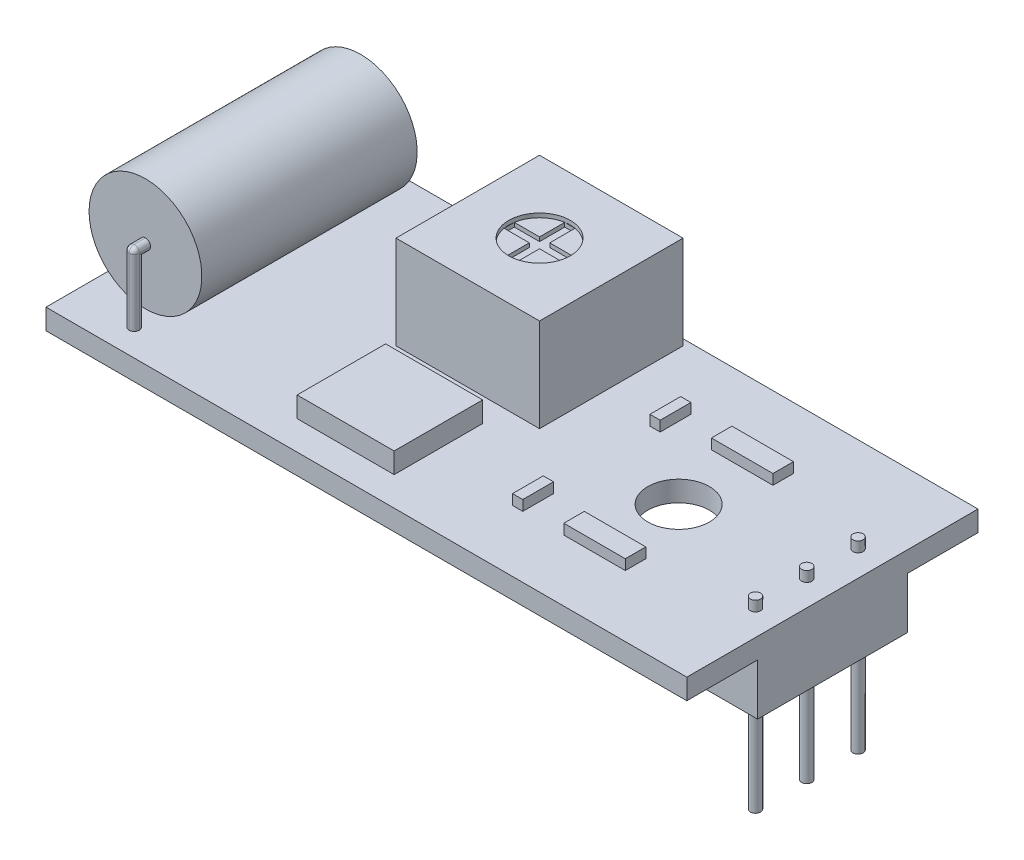
SolidWorks part; units mm, degrees
ref_plane "Plan de face" through (0, 0, 0) normal (0, 0, 1) x (1, 0, 0)
ref_plane "Plan de dessus" through (0, 0, 0) normal (0, 1, 0) x (1, 0, 0)
ref_plane "Plan de droite" through (0, 0, 0) normal (1, 0, 0) x (0, 0, -1)
sketch "Esquisse1" plane through (0, 0, 0) normal (0, 1, 0) x (1, 0, 0)
  line L1 (0, 0) -> (-31.25, 0)
  line L2 (0, 0) -> (0, 14.2)
  line L3 (0, 14.2) -> (-31.25, 14.2)
  line L4 (-31.25, 0) -> (-31.25, 14.2)
  dimension "D1" = 31.25
  dimension "D2" = 14.2
extrude "Boss.-Extru.1" add sketch "Esquisse1" along normal blind 1
sketch "Esquisse2" plane through (0, 1, 0) normal (0, 1, 0) x (1, 0, 0)
  line L0 (-31.25, 14.2) -> (-28.25, 14.2) construction
  line L1 (0, 14.2) -> (-31.25, 14.2) construction
  line L2 (-28.25, 14.2) -> (-28.25, 0) construction
  line L3 (-31.25, 0) -> (0, 0) construction
  line L4 (-28.25, 0) -> (-31.25, 0) construction
  line L5 (-28.25, 14.2) -> (-28.25, 12.9) construction
  line L6 (-28.25, 0) -> (-28.25, 1.3) construction
  line L8 (-28, 12.65) -> (-28.5, 12.65)
  line L9 (-28, 12.65) -> (-28, 13.15)
  line L10 (-28, 13.15) -> (-28.5, 13.15)
  line L11 (-28.5, 12.65) -> (-28.5, 13.15)
  line L12 (-28, 12.65) -> (-28.5, 13.15) construction
  line L13 (-28, 13.15) -> (-28.5, 12.65) construction
  line L14 (-28, 1.05) -> (-28.5, 1.05)
  line L15 (-28, 1.05) -> (-28, 1.55)
  line L16 (-28, 1.55) -> (-28.5, 1.55)
  line L17 (-28.5, 1.05) -> (-28.5, 1.55)
  line L18 (-28, 1.05) -> (-28.5, 1.55) construction
  line L19 (-28, 1.55) -> (-28.5, 1.05) construction
  dimension "D1" = 3
  dimension "D2" = 1.3
  dimension "D3" = 1.3
  dimension "D4" = 0.5
  dimension "D5" = 0.5
  dimension "D6" = 0.5
  dimension "D7" = 0.5
extrude "Boss.-Extru.2" add sketch "Esquisse2" along normal blind 3.5
sketch "Esquisse3" plane through (0, 0, -12.65) normal (0, 0, 1) x (1, 0, 0)
  line L0 (-28.5, 4.5) -> (-28.5, 1) construction
  line L1 (-28, 4.5) -> (-28.5, 4.5)
  line L2 (-28, 4.5) -> (-28, 4)
  line L3 (-28, 4) -> (-28.5, 4)
  line L4 (-28.5, 4.5) -> (-28.5, 4)
  dimension "D1" = 0.5
extrude "Boss.-Extru.3" add sketch "Esquisse3" along normal blind 0.3
sketch "Esquisse4" plane through (0, 0, -1.55) normal (0, 0, -1) x (-1, 0, 0)
  line L0 (28, 4.5) -> (28, 1) construction
  line L1 (28.5, 4.5) -> (28, 4.5)
  line L2 (28.5, 4.5) -> (28.5, 4)
  line L3 (28.5, 4) -> (28, 4)
  line L4 (28, 4.5) -> (28, 4)
  dimension "D1" = 0.5
extrude "Boss.-Extru.4" add sketch "Esquisse4" along normal blind 0.3
sketch "Esquisse5" plane through (0, 0, -12.35) normal (0, 0, 1) x (1, 0, 0)
  line L0 (-28.5, 4.5) -> (-28, 4) construction
  circle A0 centre (-28.25, 4.25) radius 2.75
  dimension "D1" = 5.5
extrude "Boss.-Extru.5" add sketch "Esquisse5" along normal blind 10.5
sketch "Esquisse6" plane through (0, 1, 0) normal (0, 1, 0) x (1, 0, 0)
  line L0 (0, 14.2) -> (-31.25, 14.2) construction
  line L1 (-21.0823, 6.9) -> (-14.0823, 6.9)
  line L2 (-21.0823, 6.9) -> (-21.0823, 13.9)
  line L3 (-21.0823, 13.9) -> (-14.0823, 13.9)
  line L4 (-14.0823, 6.9) -> (-14.0823, 13.9)
  dimension "D1" = 7
  dimension "D2" = 7
  dimension "D3" = 0.3
extrude "Boss.-Extru.6" add sketch "Esquisse6" along normal blind 4.55
sketch "Esquisse7" plane through (0, 5.55, 0) normal (0, 1, 0) x (1, 0, 0)
  line L0 (-21.0823, 6.9) -> (-14.0823, 13.9) construction
  line L1 (-14.0823, 13.9) -> (-21.0823, 13.9) construction
  line L2 (-14.0823, 13.9) -> (-21.0823, 13.9) construction
  circle A0 centre (-17.5823, 10.4) radius 1.5
  dimension "D1" = 3
extrude "Enlèv. mat.-Extru.1" cut sketch "Esquisse7" against normal blind 0.2
sketch "Esquisse8" plane through (0, 5.35, 0) normal (0, 1, 0) x (1, 0, 0)
  line L0 (-21.0823, 6.9) -> (-14.0823, 13.9) construction
  line L2 (-16.1032, 10.65) -> (-19.0613, 10.65)
  line L3 (-16.1032, 10.65) -> (-16.1032, 10.15)
  line L4 (-16.1032, 10.15) -> (-19.0613, 10.15)
  line L5 (-19.0613, 10.65) -> (-19.0613, 10.15)
  line L6 (-16.1032, 10.65) -> (-19.0613, 10.15) construction
  line L7 (-16.1032, 10.15) -> (-19.0613, 10.65) construction
  line L8 (-17.3323, 11.879) -> (-17.8323, 11.879)
  line L9 (-17.3323, 11.879) -> (-17.3323, 8.921)
  line L10 (-17.3323, 8.921) -> (-17.8323, 8.921)
  line L11 (-17.8323, 11.879) -> (-17.8323, 8.921)
  line L12 (-17.3323, 11.879) -> (-17.8323, 8.921) construction
  line L13 (-17.3323, 8.921) -> (-17.8323, 11.879) construction
  circle A0 centre (-17.5823, 10.4) radius 1.5 construction
  circle A1 centre (-17.5823, 10.4) radius 1.5 construction
  point P4 (-17.5823, 10.4)
  point P11 (-17.5823, 10.4)
  dimension "D1" = 0.5
  dimension "D2" = 0.5
extrude "Enlèv. mat.-Extru.2" cut sketch "Esquisse8" against normal blind 0.2 contours L11 L2 L5 L4 | L4 L11 L10 L9 | L2 L9 L4 L3 | L8 L11 L2 L9 | L2 L11 L4 L9 region at (-16.7177, 5.35, -10.4) region at (-17.5823, 5.35, -10.4) region at (-17.5823, 5.35, -11.2645) region at (-18.4468, 5.35, -10.4) region at (-17.5823, 5.35, -9.5355)
sketch "Esquisse9" plane through (0, 1, 0) normal (0, 1, 0) x (1, 0, 0)
  line L0 (-31.25, 0) -> (0, 0) construction
  line L1 (-20.4183, 1.4145) -> (-15.6873, 1.4145)
  line L2 (-20.4183, 1.4145) -> (-20.4183, 5.7305)
  line L3 (-20.4183, 5.7305) -> (-15.6873, 5.7305)
  line L4 (-15.6873, 1.4145) -> (-15.6873, 5.7305)
  line L5 (-9, 3) -> (-6, 3)
  line L6 (-9, 3) -> (-9, 4)
  line L7 (-9, 4) -> (-6, 4)
  line L8 (-6, 3) -> (-6, 4)
  line L9 (-9, 10.2) -> (-6, 10.2)
  line L10 (-9, 10.2) -> (-9, 11.2)
  line L11 (-9, 11.2) -> (-6, 11.2)
  line L12 (-6, 10.2) -> (-6, 11.2)
  line L13 (-11.5, 3) -> (-11, 3)
  line L14 (-11.5, 3) -> (-11.5, 4.5)
  line L15 (-11.5, 4.5) -> (-11, 4.5)
  line L16 (-11, 3) -> (-11, 4.5)
  line L17 (-11.5, 9.7) -> (-11, 9.7)
  line L18 (-11.5, 9.7) -> (-11.5, 11.2)
  line L19 (-11.5, 11.2) -> (-11, 11.2)
  line L20 (-11, 9.7) -> (-11, 11.2)
  line L21 (0, 14.2) -> (-31.25, 14.2) construction
  line L22 (0, 0) -> (0, 14.2) construction
  line L23 (-7.5, 4) -> (-7.5, 10.2) construction
  point P26 (-11, 3.75)
  point P27 (-11.25, 11.2)
  dimension "D1" = 1
  dimension "D2" = 1
  dimension "D3" = 3
  dimension "D4" = 3
  dimension "D5" = 1.5
  dimension "D6" = 1.5
  dimension "D7" = 0.5
  dimension "D8" = 0.5
  dimension "D9" = 3
  dimension "D10" = 3
  dimension "D11" = 6
  dimension "D12" = 6
  dimension "D13" = 2
  dimension "D14" = 2
  dimension "D15" = 0
  dimension "D16" = 0
extrude "Boss.-Extru.7" add sketch "Esquisse9" along normal blind 0.5
sketch "Esquisse10" plane through (0, 1.5, 0) normal (0, 1, 0) x (1, 0, 0)
  line L1 (-20.4183, 1.4145) -> (-15.6873, 1.4145)
  line L2 (-20.4183, 1.4145) -> (-20.4183, 5.7305)
  line L3 (-20.4183, 5.7305) -> (-15.6873, 5.7305)
  line L4 (-15.6873, 1.4145) -> (-15.6873, 5.7305)
extrude "Boss.-Extru.8" add sketch "Esquisse10" along normal blind 0.5
sketch "Esquisse11" plane through (0, 1, 0) normal (0, 1, 0) x (1, 0, 0)
  line L0 (-7.5, 4) -> (-7.5, 10.2) construction
  line L1 (-6, 4) -> (-9, 4) construction
  line L2 (-9, 10.2) -> (-6, 10.2) construction
  circle A0 centre (-7.5, 7.1) radius 1.5
  dimension "D1" = 3
extrude "Enlèv. mat.-Extru.3" cut sketch "Esquisse11" against normal blind 22.5
sketch "Esquisse12" plane through (0, 0, 0) normal (0, -1, 0) x (-1, 0, 0)
  line L0 (0, 0) -> (0, 14.2) construction
  line L1 (0, 10.75) -> (2.5, 10.75)
  line L2 (0, 10.75) -> (0, 3.45)
  line L3 (0, 3.45) -> (2.5, 3.45)
  line L4 (2.5, 10.75) -> (2.5, 3.45)
  line L5 (0, 14.2) -> (31.25, 14.2) construction
  dimension "D1" = 7.3
  dimension "D2" = 3.45
  dimension "D3" = 2.5
extrude "Boss.-Extru.9" add sketch "Esquisse12" along normal blind 2.5
sketch "Esquisse13" plane through (0, -2.5, 0) normal (0, -1, 0) x (-1, 0, 0)
  line L0 (1.25, 10.75) -> (1.25, 9.6) construction
  line L1 (2.5, 10.75) -> (0, 10.75) construction
  line L2 (1.25, 9.6) -> (1.25, 4.1615) construction
  line L3 (1.25, 4.1615) -> (1.25, 3.45) construction
  line L4 (0, 3.45) -> (2.5, 3.45) construction
  circle A0 centre (1.25, 9.6) radius 0.25
  circle A1 centre (1.25, 7.1) radius 0.25
  circle A2 centre (1.25, 4.6) radius 0.25
  dimension "D2" = 0.5
  dimension "D1" = 1.15
  dimension "D3" = 3
extrude "Boss.-Extru.10" add sketch "Esquisse13" along normal blind 5 and the other way blind 4
fillet "Congé1" radius 0.25 4 edges at (-28.5, 2.5, -1.55) (-28, 2.75, -1.05) (-28, 2.5, -1.55) (-28.5, 2.75, -1.05)
fillet "Congé2" radius 0.25 6 edges at (-28.5, 4, -1.575) (-28, 4, -1.575) (-28.4268, 4.5, -1.1232) (-28.0732, 4.5, -1.1232) (-28.5, 4.5, -1.575) (-28, 4.5, -1.575)
fillet "Congé3" radius 0.25 8 edges at (-28, 4, -12.5) (-28, 2.5, -12.65) (-28, 2.75, -13.15) (-28, 4.5, -12.75) (-28.5, 2.5, -12.65) (-28.5, 4, -12.5) (-28.5, 4.5, -12.75) (-28.5, 2.75, -13.15)
